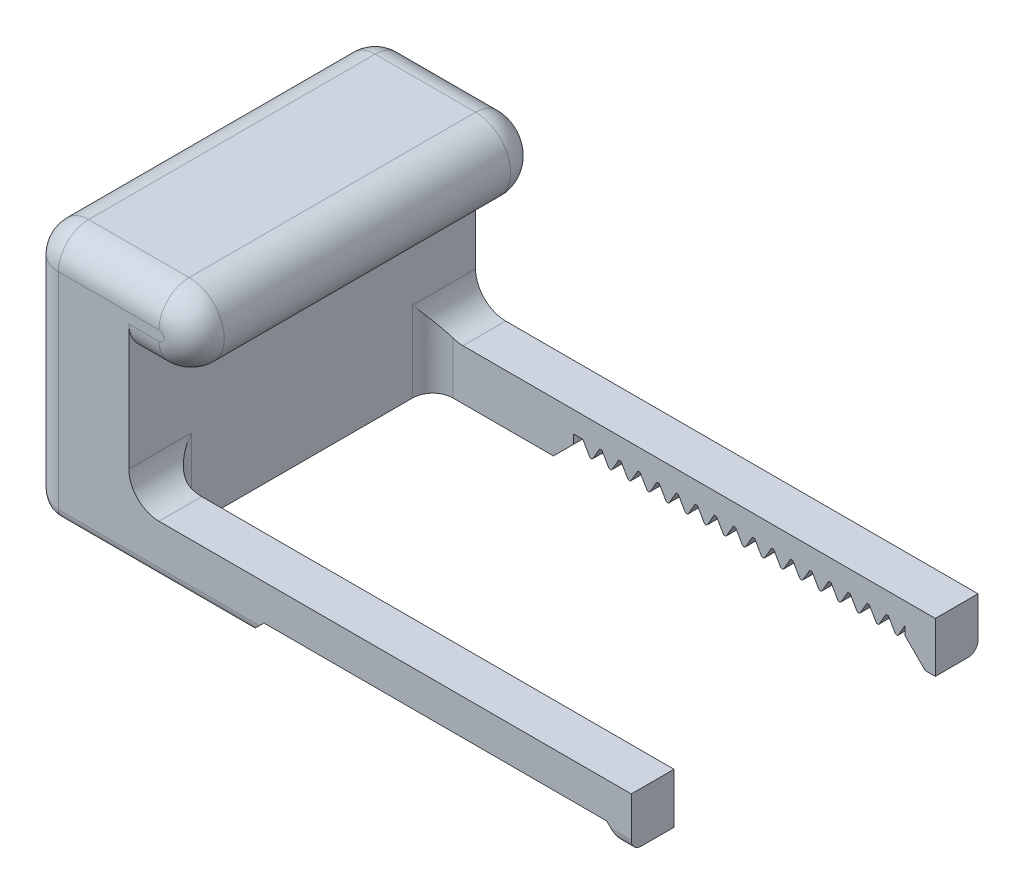
SolidWorks part; units mm, degrees
ref_plane "Front" through (0, 0, 0) normal (0, 0, 1) x (1, 0, 0)
ref_plane "Top" through (0, 0, 0) normal (0, 1, 0) x (1, 0, 0)
ref_plane "Right" through (0, 0, 0) normal (1, 0, 0) x (0, 0, -1)
sketch "Sketch1" plane through (0, 0, 0) normal (0, 1, 0) x (1, 0, 0)
  line L0 (0, 13) -> (0, -13)
  line L1 (0, 17.25) -> (-10, 17.25)
  line L2 (0, -17.25) -> (-10, -17.25)
  line L3 (-10, 17.25) -> (-10, -17.25)
  line L5 (0, 17.25) -> (50, 17.25)
  line L6 (0, 13) -> (50, 13)
  line L7 (50, 17.25) -> (50, 13)
  line L9 (0, -17.25) -> (50, -17.25)
  line L10 (0, -13) -> (50, -13)
  line L11 (50, -17.25) -> (50, -13)
  point P0 (0, 0)
  dimension "D1" = 10
  dimension "D2" = 4.25
  dimension "D3" = 26
  dimension "D4" = 50
extrude "Boss-Extrude1" add sketch "Sketch1" along normal blind 5
sketch "Sketch2" plane through (0, 5, 0) normal (0, 1, 0) x (1, 0, 0)
  line L0 (-10, -17.25) -> (50, -17.25) construction
  line L1 (-10, 17.25) -> (0, 17.25)
  line L2 (-10, 17.25) -> (-10, -17.25)
  line L3 (-10, -17.25) -> (0, -17.25)
  line L4 (0, 17.25) -> (0, -17.25)
  line L5 (0, -13) -> (0, 13) construction
extrude "Boss-Extrude2" add sketch "Sketch2" along normal blind 19.5
fillet "Fillet1" radius 3 2 edges at (0, 5, -15.125) (0, 5, 15.125)
fillet "Fillet2" radius 2 2 edges at (0, 4, 13) (0, 4, -13)
sketch "Sketch4" plane through (0, 0, 17.25) normal (0, 0, 1) x (1, 0, 0)
  line L1 (3, 17.5) -> (0, 17.5)
  line L2 (0, 24.5) -> (0, 8) construction
  line L3 (0, 17.5) -> (0, 24.5)
  line L4 (0, 24.5) -> (3, 24.5)
  arc A0 (3, 24.5) -> (3, 17.5) centre (3, 21) cw
  dimension "D1" = 7
  dimension "D2" = 3
extrude "Boss-Extrude3" add sketch "Sketch4" against normal up to surface (34.5 mm away) up to face at (11.7684, 9.4827, -17.25)
fillet "Fillet3" radius 3 10 edges at (-3.5, 24.5, -17.25) (6.5, 21, -17.25) (1.5, 17.5, 17.25) (-3.5, 24.5, 17.25) (1.5, 17.5, -17.25) (-10, 24.5, 0) (-10, 0, 0) (-10, 12.25, -17.25) (-10, 12.25, 17.25) (6.5, 21, 17.25)
sketch "Sketch5" plane through (0, 0, 17.25) normal (0, 0, 1) x (1, 0, 0)
  line L1 (47, 2.9) -> (14, 2.9)
  line L2 (47, 2.9) -> (47, 0)
  line L3 (47, 0) -> (14, 0)
  line L4 (14, 2.9) -> (14, 0)
  line L5 (-7, 0) -> (50, 0) construction
  line L6 (50, 5) -> (50, 0) construction
  dimension "D1" = 33
  dimension "D2" = 2.9
  dimension "D3" = 3
extrude "Cut-Extrude1" cut sketch "Sketch5" against normal through all
fillet "Fillet4" [suppressed] radius 1
chamfer "Chamfer1" distance 2 angle 45 4 edges at (14, 0, -15.125) (14, 0, 15.125) (47, 0, 15.125) (47, 0, -15.125)
sketch "Sketch6" plane through (0, 0, 17.25) normal (0, 0, 1) x (1, 0, 0)
  line L1 (47, 2.9) -> (46.1628, 1.45)
  line L3 (46.1628, 1.45) -> (45.3257, 2.9)
  line L4 (47, 2.9) -> (14, 2.9) construction
  line L5 (45.3257, 2.9) -> (47, 2.9)
  dimension "D1" = 60
  dimension "D2" = 1.45
extrude "Boss-Extrude4" add sketch "Sketch6" against normal up to surface (34.5 mm away) up to face at (18.5252, 7.4119, -17.25)
pattern_linear "LPattern1" count 17 spacing 1.9 along (-1, 0, 0) of "Boss-Extrude4"
sketch "Sketch7" plane through (0, 2.9, 0) normal (0, 1, 0) x (-1, 0, 0)
  line L0 (-2, -13) -> (-12, -13) construction
  line L1 (-12, 13) -> (-50, 13)
  line L2 (-12, 13) -> (-12, -13)
  line L3 (-12, -13) -> (-50, -13)
  line L4 (-50, 13) -> (-50, -13)
  line L5 (-50, 17.25) -> (-50, 13) construction
  line L6 (-3, -13) -> (-50, -13) construction
extrude "Cut-Extrude2" cut sketch "Sketch7" against normal through all
sketch "Sketch9" plane through (0, 0, 17.25) normal (0, 0, 1) x (1, 0, 0)
  line L0 (12, 1.45) -> (49, 1.45)
  line L1 (49, 1.45) -> (49, 5)
  line L2 (3, 5) -> (50, 5) construction
  line L3 (49, 5) -> (12, 5)
  line L4 (12, 5) -> (12, 1.45)
extrude "Boss-Extrude5" add sketch "Sketch9" against normal up to surface (4.25 mm away) up to face at (29.8705, 2.3816, 13)
fillet "Fillet5" radius 1 6 edges at (-9.1213, 0.8787, -16.3713) (-9.1213, 0.8787, 16.3713) (2.5, 0, -17.25) (2.5, 0, 17.25) (49.5, 0, 17.25) (49.5, 0, -17.25)
fillet "Fillet6" radius 0.2 17 edges at (46.1628, 1.45, -15.125) (44.2628, 1.45, -15.125) (42.3628, 1.45, -15.125) (40.4628, 1.45, -15.125) (38.5628, 1.45, -15.125) (36.6628, 1.45, -15.125) (34.7628, 1.45, -15.125) (32.8628, 1.45, -15.125) (30.9628, 1.45, -15.125) (29.0628, 1.45, -15.125) (27.1628, 1.45, -15.125) (25.2628, 1.45, -15.125) (23.3628, 1.45, -15.125) (21.4628, 1.45, -15.125) (19.5628, 1.45, -15.125) (17.6628, 1.45, -15.125) (15.7628, 1.45, -15.125)
